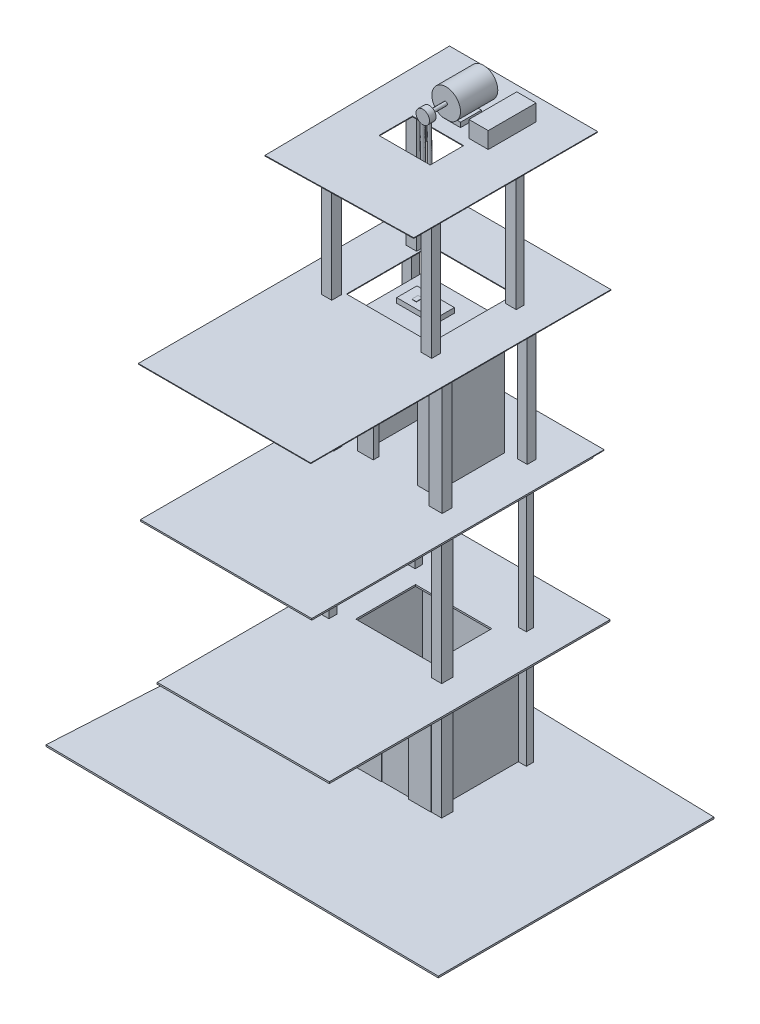
SolidWorks part; units mm, degrees
ref_plane "Front Plane" through (0, 0, 0) normal (0, 0, 1) x (1, 0, 0)
ref_plane "Top Plane" through (0, 0, 0) normal (0, 1, 0) x (1, 0, 0)
ref_plane "Right Plane" through (0, 0, 0) normal (1, 0, 0) x (0, 0, -1)
sketch "Sketch1" plane through (0, 0, 0) normal (0, 1, 0) x (1, 0, 0)
  line L1 (-1119.5185, 584.2256) -> (1199.1194, 522.7665)
  line L2 (-1119.5185, 584.2256) -> (-1218.0451, -1131.0237)
  line L3 (-1218.0451, -1131.0237) -> (1199.1194, -1157.1766)
  line L4 (1199.1194, 522.7665) -> (1199.1194, -1157.1766)
  line L5 (-1119.5185, 584.2256) -> (1199.1194, -1157.1766) construction
  line L6 (-1218.0451, -1131.0237) -> (1199.1194, 522.7665) construction
  point P0 (0, 0)
  point P5 (-1081.5805, 623.8739)
  point P6 (1586.8831, -1195.646)
  point P7 (1127.9589, 475.4185)
  point P8 (1273.4422, -1106.673)
  point P9 (-1033.4428, 518.7999)
  point P10 (1127.9589, -1075.7859)
  point P11 (1094.021, 455.5568)
  point P12 (-2669.2134, -1078.1469)
  point P13 (-2449.8772, 1011.6691)
  point P14 (-1119.5185, 584.2256)
  point P15 (-1234.8964, -941.8705)
  point P16 (-1218.0451, -1131.0237)
  point P17 (1199.1194, -1157.1766)
extrude "Boss-Extrude1" add sketch "Sketch1" along normal blind 10
sketch "Sketch2" plane through (0, 10, 0) normal (0, 1, 0) x (1, 0, 0)
  line L1 (-310.9875, 262.3228) -> (311.3377, 262.3228)
  line L2 (-310.9875, 262.3228) -> (-310.9875, -313.9536)
  line L3 (-310.9875, -313.9536) -> (311.3377, -313.9536)
  line L4 (311.3377, 262.3228) -> (311.3377, -313.9536)
  line L5 (-272.0145, 218.0111) -> (278.8911, 218.0111)
  line L6 (-272.0145, 218.0111) -> (-272.0145, -277.642)
  line L7 (-272.0145, -277.642) -> (278.8911, -277.642)
  line L8 (278.8911, 218.0111) -> (278.8911, -277.642)
extrude "Boss-Extrude2" add sketch "Sketch2" along normal blind 700
sketch "Sketch3" plane through (0, 710, 0) normal (0, 1, 0) x (1, 0, 0)
  line L1 (-498.5759, 538.5603) -> (550.6847, 538.5603)
  line L2 (-498.5759, 538.5603) -> (-498.5759, -1173.1855)
  line L3 (-498.5759, -1173.1855) -> (550.6847, -1173.441)
  line L4 (550.6847, 538.5603) -> (550.6847, -1173.441)
extrude "Boss-Extrude3" add sketch "Sketch3" along normal blind 10
sketch "Sketch4" plane through (0, 0, 313.9536) normal (0, 0, 1) x (1, 0, 0)
  line L1 (-169.9016, 641.4575) -> (173.8441, 641.4575)
  line L2 (-169.9016, 641.4575) -> (-169.9016, 10)
  line L3 (-169.9016, 10) -> (173.8441, 10)
  line L4 (173.8441, 641.4575) -> (173.8441, 10)
extrude "Cut-Extrude1" cut sketch "Sketch4" against normal blind 40
sketch "Sketch5" plane through (0, 0, 313.9536) normal (0, 0, 1) x (1, 0, 0)
  line L1 (-283.6713, 474.5331) -> (-187.5856, 474.5331)
  line L2 (-283.6713, 474.5331) -> (-283.6713, 265.4455)
  line L3 (-283.6713, 265.4455) -> (-187.5856, 265.4455)
  line L4 (-187.5856, 474.5331) -> (-187.5856, 265.4455)
extrude "Boss-Extrude4" add sketch "Sketch5" along normal blind 1
sketch "Sketch6" plane through (0, 0, 314.9536) normal (0, 0, 1) x (1, 0, 0)
  line L1 (-271.1746, 418.75) -> (-195.647, 418.75)
  line L2 (-271.1746, 418.75) -> (-271.1746, 375.0617)
  line L3 (-271.1746, 375.0617) -> (-195.647, 375.0617)
  line L4 (-195.647, 418.75) -> (-195.647, 375.0617)
extrude "Cut-Extrude2" cut sketch "Sketch6" against normal blind 1
sketch "Sketch7" plane through (0, 0, 314.9536) normal (0, 0, 1) x (1, 0, 0)
  circle A0 centre (-236.0757, 343.6172) radius 20.2971
  circle A1 centre (-236.0757, 291.5015) radius 20.232
extrude "Boss-Extrude5" add sketch "Sketch7" along normal blind 1
sketch "Sketch8" plane through (0, 0, 315.9536) normal (0, 0, 1) x (1, 0, 0)
  line L0 (-248.1005, 334.3432) -> (-224.1168, 334.3432)
  line L1 (-224.1168, 334.3432) -> (-236.1087, 356.5701)
  line L2 (-236.1087, 356.5701) -> (-248.1005, 334.3432)
  line L3 (-248.1005, 300.7341) -> (-224.1168, 300.7341)
  line L4 (-224.1168, 300.7341) -> (-236.1087, 278.0211)
  line L5 (-236.1087, 278.0211) -> (-248.1005, 300.7341)
extrude "Boss-Extrude6" add sketch "Sketch8" along normal blind 1
sketch "Sketch9" plane through (-169.9016, 0, 0) normal (1, 0, 0) x (0, 0, -1)
  line L1 (-304.9322, 641.4575) -> (-277.642, 641.4575)
  line L2 (-304.9322, 641.4575) -> (-304.9322, 10)
  line L3 (-304.9322, 10) -> (-277.642, 10)
  line L4 (-277.642, 641.4575) -> (-277.642, 10)
extrude "Boss-Extrude7" add sketch "Sketch9" along normal blind 170
sketch "Sketch10" plane through (0.0984, 0, 0) normal (1, 0, 0) x (0, 0, -1)
  line L1 (-301.4683, 640.5034) -> (-277.642, 640.5034)
  line L2 (-301.4683, 640.5034) -> (-301.4683, 10)
  line L3 (-301.4683, 10) -> (-277.642, 10)
  line L4 (-277.642, 640.5034) -> (-277.642, 10)
extrude "Boss-Extrude8" add sketch "Sketch10" along normal blind 170
sketch "Sketch11" plane through (0, 0, 313.9536) normal (0, 0, 1) x (1, 0, 0)
  line L1 (-53.7077, 693.9278) -> (48.7244, 693.9278)
  line L2 (-53.7077, 693.9278) -> (-53.7077, 651.2448)
  line L3 (-53.7077, 651.2448) -> (48.7244, 651.2448)
  line L4 (48.7244, 693.9278) -> (48.7244, 651.2448)
extrude "Boss-Extrude9" add sketch "Sketch11" along normal blind 1
sketch "Sketch12" plane through (0, 0, 314.9536) normal (0, 0, 1) x (1, 0, 0)
  line L1 (-47.5467, 689.1219) -> (41.8868, 689.1219)
  line L2 (-47.5467, 689.1219) -> (-47.5467, 655.2159)
  line L3 (-47.5467, 655.2159) -> (41.8868, 655.2159)
  line L4 (41.8868, 689.1219) -> (41.8868, 655.2159)
extrude "Cut-Extrude3" cut sketch "Sketch12" against normal blind 1
sketch "Sketch13" plane through (0, 0, 313.9536) normal (0, 0, 1) x (1, 0, 0)
  line L0 (-16.1887, 682.3335) -> (-12.3636, 682.3335)
  line L1 (-12.3636, 682.3335) -> (-16.2809, 666.1802)
  line L2 (-16.2809, 666.1802) -> (-10.8261, 666.1802)
  line L3 (-5.3714, 666.1802) -> (-5.3714, 662.7972)
  line L4 (-5.3714, 662.7972) -> (-7.9099, 662.7972)
  line L5 (-21.2894, 662.7972) -> (-16.1887, 682.3335)
  line L6 (-10.8261, 671.5233) -> (-10.8261, 666.1802)
  line L7 (-10.8261, 659.937) -> (-7.9099, 659.937)
  line L8 (-7.9099, 659.937) -> (-7.9099, 662.7972)
  line L9 (-7.9099, 671.5233) -> (-10.8261, 671.5233)
  line L10 (-10.8261, 662.7972) -> (-10.8261, 659.937)
  line L11 (-7.9099, 666.1802) -> (-5.3714, 666.1802)
  line L12 (-7.9099, 666.1802) -> (-7.9099, 671.5233)
  line L13 (-10.8261, 662.7972) -> (-21.2894, 662.7972)
extrude "Boss-Extrude10" add sketch "Sketch13" along normal blind 1
sketch "Sketch14" plane through (0, 0, 313.9536) normal (0, 0, 1) x (1, 0, 0)
  line L0 (8.2825, 678.5261) -> (25.4536, 678.5261)
  line L1 (25.4536, 678.5261) -> (16.868, 660.4022)
  line L2 (16.868, 660.4022) -> (8.2825, 678.5261)
extrude "Boss-Extrude11" add sketch "Sketch14" along normal blind 1
sketch "Sketch15" plane through (0, 0, 313.9536) normal (0, 0, 1) x (1, 0, 0)
  line L0 (-253.3924, 406.4083) -> (-253.3924, 387.5651)
  line L1 (-253.3924, 387.5651) -> (-258.9323, 387.5651)
  line L2 (-258.9323, 387.5651) -> (-258.9323, 385.0304)
  line L3 (-258.9323, 385.0304) -> (-244.3761, 385.0304)
  line L4 (-244.3761, 385.0304) -> (-244.3761, 387.5681)
  line L5 (-244.3761, 387.5681) -> (-249.8802, 387.5681)
  line L6 (-249.8802, 387.5681) -> (-249.8802, 410.5631)
  line L7 (-249.8802, 410.5631) -> (-259.6929, 410.2522)
  line L8 (-259.6929, 410.2522) -> (-259.5666, 406.4083)
  line L9 (-259.5666, 406.4083) -> (-253.3924, 406.4083)
extrude "Boss-Extrude12" add sketch "Sketch15" along normal blind 1
sketch "Sketch16" plane through (0, 0, 313.9536) normal (0, 0, 1) x (1, 0, 0)
  line L0 (-235.6485, 408.4658) -> (-235.6485, 385.5858)
  line L1 (-235.6485, 385.5858) -> (-232.1063, 385.5858)
  line L2 (-232.1063, 385.5858) -> (-232.2231, 401.9914)
  line L3 (-235.6485, 408.4658) -> (-231.8951, 408.4658)
  line L4 (-231.8951, 408.4658) -> (-231.8951, 406.5499)
  line L5 (-221.9834, 403.0568) -> (-221.9834, 385.5858)
  line L6 (-221.9834, 385.5858) -> (-218.8212, 385.5858)
  line L7 (-218.8212, 385.5858) -> (-219.0863, 397.9701)
  line L8 (-208.8863, 401.5917) -> (-208.8863, 385.5858)
  line L9 (-208.8863, 385.5858) -> (-206.271, 385.5858)
  line L10 (-206.271, 385.5858) -> (-206.5126, 401.9271)
  line L11 (-219.2828, 403.1887) -> (-219.0863, 397.9701)
  arc A4 (-221.9834, 403.0568) -> (-232.2231, 401.9914) centre (-226.8379, 399.9737) ccw
  arc A6 (-208.8863, 401.5917) -> (-219.2828, 403.1887) centre (-214.4049, 400.3049) ccw
  arc A7 (-206.5126, 401.9271) -> (-220.6047, 405.4509) centre (-214.4049, 400.3049) ccw
  arc A8 (-220.6047, 405.4509) -> (-231.8951, 406.6078) centre (-226.8379, 400.2912) ccw
  line M5 (-271.1746, 418.75) -> (-271.1746, 375.0617)
  line M6 (-271.1746, 375.0617) -> (-195.647, 375.0617)
  line M7 (-195.647, 375.0617) -> (-195.647, 418.75)
  line M8 (-195.647, 418.75) -> (-271.1746, 418.75)
  line M9 (-253.3924, 387.5651) -> (-253.3924, 406.4083)
  line M10 (-253.3924, 406.4083) -> (-259.5666, 406.4083)
  line M11 (-259.5666, 406.4083) -> (-259.6929, 410.2522)
  line M12 (-259.6929, 410.2522) -> (-249.8802, 410.5631)
  line M13 (-249.8802, 410.5631) -> (-249.8802, 387.5681)
  line M14 (-249.8802, 387.5681) -> (-244.3761, 387.5681)
  line M15 (-244.3761, 387.5681) -> (-244.3761, 385.0304)
  line M16 (-244.3761, 385.0304) -> (-258.9323, 385.0304)
  line M17 (-258.9323, 385.0304) -> (-258.9323, 387.5651)
  line M18 (-258.9323, 387.5651) -> (-253.3924, 387.5651)
extrude "Cut-Extrude4" cut sketch "Sketch16" against normal blind 2 contours A8 A7 L10 L9 L8 A6 L11 L7 L6 L5 A4 L2 L1 L0 L3 L4 M8 M5 M6 M7 M18 M9 M10 M11 M12 M13 M14 M15 M16 M17 region at (-233.4108, 417.8775, 313.9536)
sketch "Sketch17" plane through (0, 0, 311.9536) normal (0, 0, 1) x (1, 0, 0)
  line L1 (-271.2094, 458.8572) -> (-195.647, 458.8572)
  line L2 (-271.2094, 458.8572) -> (-271.2094, 418.4414)
  line L3 (-271.2094, 418.4414) -> (-195.7041, 418.4414)
  line L4 (-195.647, 458.8572) -> (-195.7041, 418.4414)
extrude "Cut-Extrude5" cut sketch "Sketch17" against normal blind 1
sketch "Sketch18" plane through (0, 0, 314.9536) normal (0, 0, 1) x (1, 0, 0)
  line L1 (-271.1417, 456.7599) -> (-195.647, 456.7599)
  line L2 (-271.1417, 456.7599) -> (-271.1417, 418.75)
  line L3 (-271.1417, 418.75) -> (-195.647, 418.75)
  line L4 (-195.647, 456.7599) -> (-195.647, 418.75)
extrude "Cut-Extrude6" cut sketch "Sketch18" against normal blind 3
sketch "Sketch19" plane through (0, 0, 310.9536) normal (0, 0, 1) x (1, 0, 0)
  line L0 (-254.3129, 446.7406) -> (-254.3129, 426.3557)
  line L1 (-254.3129, 426.3557) -> (-259.3962, 426.3557)
  line L2 (-259.3962, 426.3557) -> (-259.3962, 423.275)
  line L3 (-259.3962, 423.275) -> (-244.6783, 423.275)
  line L4 (-244.6783, 423.275) -> (-244.6783, 426.3453)
  line L5 (-244.6783, 426.3453) -> (-250.7281, 426.3453)
  line L6 (-250.7281, 426.3453) -> (-250.7281, 450.1154)
  line L7 (-250.7281, 450.1154) -> (-259.3962, 450.1154)
  line L8 (-259.3962, 450.1154) -> (-259.3962, 446.7406)
  line L9 (-259.3962, 446.7406) -> (-254.3129, 446.7406)
extrude "Boss-Extrude14" add sketch "Sketch19" along normal blind 2
sketch "Sketch20" plane through (0, 0, 310.9536) normal (0, 0, 1) x (1, 0, 0)
  line L0 (-231.7389, 449.8367) -> (-231.7389, 423.3615)
  line L1 (-231.7389, 423.3615) -> (-228.298, 423.3615)
  line L2 (-228.298, 423.3615) -> (-228.1456, 436.3278)
  line L3 (-231.7389, 449.8367) -> (-231.7389, 450.2937)
  line L4 (-231.7389, 450.2937) -> (-228.6156, 450.2937)
  line L5 (-228.6156, 450.2937) -> (-228.5661, 449.4447)
  line L6 (-228.5661, 446.4929) -> (-228.298, 439.2366)
  arc A0 (-228.1456, 436.3278) -> (-228.5661, 449.4447) centre (-224.524, 443.0091) ccw
  arc A1 (-228.298, 439.2366) -> (-228.5661, 446.4929) centre (-224.524, 443.0091) ccw
extrude "Boss-Extrude15" add sketch "Sketch20" along normal blind 2
sketch "Sketch21" plane through (0, 10, 0) normal (0, 1, 0) x (1, 0, 0)
  line L1 (-370.2495, 258.4828) -> (-312.2078, 258.4828)
  line L2 (-370.2495, 258.4828) -> (-370.2495, 212.8366)
  line L3 (-370.2495, 212.8366) -> (-312.2078, 212.8366)
  line L4 (-312.2078, 258.4828) -> (-312.2078, 212.8366)
  line L5 (-365.6413, -265.0657) -> (-310.9875, -265.0657)
  line L6 (-365.6413, -265.0657) -> (-365.6413, -313.9536)
  line L7 (-365.6413, -313.9536) -> (-310.9875, -313.9536)
  line L8 (-310.9875, -265.0657) -> (-310.9875, -313.9536)
  line L9 (311.5366, -242.3922) -> (375.3624, -242.3922)
  line L10 (311.5366, -242.3922) -> (311.5366, -312.5459)
  line L11 (311.5366, -312.5459) -> (375.3624, -312.5459)
  line L12 (375.3624, -242.3922) -> (375.3624, -312.5459)
  line L13 (311.3377, 262.3228) -> (359.7161, 262.3228)
  line L14 (311.3377, 262.3228) -> (311.3377, 218.7516)
  line L15 (311.3377, 218.7516) -> (359.7161, 218.7516)
  line L16 (359.7161, 262.3228) -> (359.7161, 218.7516)
  point P16 (345.8031, 229.2992)
extrude "Boss-Extrude16" add sketch "Sketch21" along normal blind 1600
sketch "Sketch22" plane through (0, 720, 0) normal (0, 1, 0) x (1, 0, 0)
  line L1 (-227.8036, 130.7691) -> (237.8382, 130.7691)
  line L2 (-227.8036, 130.7691) -> (-227.8036, -233.8627)
  line L3 (-227.8036, -233.8627) -> (237.8382, -233.8627)
  line L4 (237.8382, 130.7691) -> (237.8382, -233.8627)
extrude "Cut-Extrude7" cut sketch "Sketch22" against normal blind 70
sketch "Sketch23" plane through (0, 1610, 0) normal (0, 1, 0) x (1, 0, 0)
  line L1 (-509.8769, 452.1824) -> (534.1888, 452.1824)
  line L2 (-509.8769, 452.1824) -> (-509.8769, -1263.8932)
  line L3 (-509.8769, -1263.8932) -> (534.1888, -1263.8932)
  line L4 (534.1888, 452.1824) -> (534.1888, -1263.8932)
extrude "Boss-Extrude18" add sketch "Sketch23" along normal blind 5
sketch "Sketch24" plane through (0, 1615, 0) normal (0, 1, 0) x (1, 0, 0)
  line L1 (-210.3928, 199.4466) -> (247.2278, 199.4466)
  line L2 (-210.3928, 199.4466) -> (-210.3928, -239.2818)
  line L3 (-210.3928, -239.2818) -> (247.2278, -239.2818)
  line L4 (247.2278, 199.4466) -> (247.2278, -239.2818)
  line L5 (-190.4374, 157.98) -> (218.1458, 157.98)
  line L6 (-190.4374, 157.98) -> (-190.4374, -203.9085)
  line L7 (-190.4374, -203.9085) -> (218.1458, -203.9085)
  line L8 (218.1458, 157.98) -> (218.1458, -203.9085)
extrude "Boss-Extrude19" add sketch "Sketch24" along normal blind 700
sketch "Sketch25" plane through (0, 0, 239.2818) normal (0, 0, 1) x (1, 0, 0)
  line L1 (-115.2948, 2253.91) -> (153.8552, 2253.91)
  line L2 (-115.2948, 2253.91) -> (-115.2948, 1615)
  line L3 (-115.2948, 1615) -> (153.8552, 1615)
  line L4 (153.8552, 2253.91) -> (153.8552, 1615)
extrude "Cut-Extrude8" cut sketch "Sketch25" against normal blind 40
sketch "Sketch26" plane through (0, 1615, 0) normal (0, 1, 0) x (1, 0, 0)
  line L1 (-392.0328, 260.8249) -> (-332.3431, 260.8249)
  line L2 (-392.0328, 260.8249) -> (-392.0328, 211.3493)
  line L3 (-392.0328, 211.3493) -> (-332.3431, 211.3493)
  line L4 (-332.3431, 260.8249) -> (-332.3431, 211.3493)
  line L5 (-362.188, -262.1021) -> (-282.7219, -262.1021)
  line L6 (-362.188, -262.1021) -> (-362.188, -314.4144)
  line L7 (-362.188, -314.4144) -> (-282.7219, -314.4144)
  line L8 (-282.7219, -262.1021) -> (-282.7219, -314.4144)
  line L9 (317.4199, 260.5296) -> (377.7458, 260.5296)
  line L10 (317.4199, 260.5296) -> (317.4199, 206.3146)
  line L11 (317.4199, 206.3146) -> (377.7458, 206.3146)
  line L12 (377.7458, 260.5296) -> (377.7458, 206.3146)
  line L13 (296.7901, -252.3262) -> (377.7458, -252.3262)
  line L14 (296.7901, -252.3262) -> (296.7901, -312.0443)
  line L15 (296.7901, -312.0443) -> (377.7458, -312.0443)
  line L16 (377.7458, -252.3262) -> (377.7458, -312.0443)
extrude "Boss-Extrude20" add sketch "Sketch26" along normal blind 800
sketch "Sketch28" plane through (0, 2315, 0) normal (0, 1, 0) x (1, 0, 0)
  line L1 (266.1556, 199.4466) -> (-253.0902, 199.4466)
  line L2 (266.1556, 199.4466) -> (266.1556, -239.2818)
  line L3 (266.1556, -239.2818) -> (-253.0902, -239.2818)
  line L4 (-253.0902, 199.4466) -> (-253.0902, -239.2818)
extrude "Boss-Extrude21" add sketch "Sketch28" along normal blind 4
sketch "Sketch29" plane through (0, 2319, 0) normal (0, 1, 0) x (1, 0, 0)
  line L1 (57.1272, 82.8953) -> (-171.3197, 82.8953)
  line L2 (57.1272, 82.8953) -> (57.1272, -40.6557)
  line L3 (57.1272, -40.6557) -> (-171.3197, -40.6557)
  line L4 (-171.3197, 82.8953) -> (-171.3197, -40.6557)
extrude "Boss-Extrude22" add sketch "Sketch29" along normal blind 30
sketch "Sketch30" plane through (0, 1615, 0) normal (0, 1, 0) x (1, 0, 0)
  line L1 (534.1888, 518.807) -> (-509.8769, 518.807)
  line L2 (534.1888, 518.807) -> (534.1888, -1263.8932)
  line L3 (534.1888, -1263.8932) -> (-509.8769, -1263.8932)
  line L4 (-509.8769, 518.807) -> (-509.8769, -1263.8932)
extrude "Boss-Extrude23" add sketch "Sketch30" along normal blind 4
sketch "Sketch31" plane through (0, 2415, 0) normal (0, 1, 0) x (1, 0, 0)
  line L1 (509.5029, 584.8272) -> (-541.0801, 584.8272)
  line L2 (509.5029, 584.8272) -> (509.5029, -1245.8933)
  line L3 (509.5029, -1245.8933) -> (-541.0801, -1245.8933)
  line L4 (-541.0801, 584.8272) -> (-541.0801, -1245.8933)
extrude "Boss-Extrude24" add sketch "Sketch31" along normal blind 4
sketch "Sketch32" plane through (0, 2419, 0) normal (0, 1, 0) x (1, 0, 0)
  line L1 (-273.2763, 267.1919) -> (241.7138, 267.1919)
  line L2 (-273.2763, 267.1919) -> (-273.2763, -244.6131)
  line L3 (-273.2763, -244.6131) -> (241.7138, -244.6131)
  line L4 (241.7138, 267.1919) -> (241.7138, -244.6131)
extrude "Cut-Extrude9" cut sketch "Sketch32" against normal blind 4
sketch "Sketch33" plane through (0, 2419, 0) normal (0, 1, 0) x (1, 0, 0)
  line L1 (-348.3927, 194.6348) -> (-285.0254, 194.6348)
  line L2 (-348.3927, 194.6348) -> (-348.3927, 250.7404)
  line L3 (-348.3927, 250.7404) -> (-285.0254, 250.7404)
  line L4 (-285.0254, 194.6348) -> (-285.0254, 250.7404)
  line L5 (-348.3927, -322.8817) -> (-285.0254, -322.8817)
  line L6 (-348.3927, -322.8817) -> (-348.3927, -262.5669)
  line L7 (-348.3927, -262.5669) -> (-285.0254, -262.5669)
  line L8 (-285.0254, -322.8817) -> (-285.0254, -262.5669)
  line L9 (260.001, -324.9173) -> (326.8178, -324.9173)
  line L10 (260.001, -324.9173) -> (260.001, -272.0698)
  line L11 (260.001, -272.0698) -> (326.8178, -272.0698)
  line L12 (326.8178, -324.9173) -> (326.8178, -272.0698)
  line L13 (260.001, 190.1754) -> (326.8178, 190.1754)
  line L14 (260.001, 190.1754) -> (260.001, 238.0831)
  line L15 (260.001, 238.0831) -> (326.8178, 238.0831)
  line L16 (326.8178, 190.1754) -> (326.8178, 238.0831)
extrude "Boss-Extrude25" add sketch "Sketch33" along normal blind 800
sketch "Sketch34" plane through (0, 3219, 0) normal (0, 1, 0) x (1, 0, 0)
  line L1 (438.8935, 574.7386) -> (-464.6289, 574.7386)
  line L2 (438.8935, 574.7386) -> (438.8935, -546.4396)
  line L3 (438.8935, -546.4396) -> (-449.6246, -565.2649)
  line L4 (-464.6289, 574.7386) -> (-449.6246, -565.2649)
  line L5 (104.6135, 91.9277) -> (-207.4731, 91.9277)
  line L6 (104.6135, 91.9277) -> (104.6135, -112.4976)
  line L7 (104.6135, -112.4976) -> (-207.4731, -112.4976)
  line L8 (-207.4731, 91.9277) -> (-207.4731, -112.4976)
extrude "Boss-Extrude26" add sketch "Sketch34" along normal blind 4
sketch "Sketch35" plane through (0, 3223, 0) normal (0, 1, 0) x (1, 0, 0)
  line L1 (-111.9386, 304.9138) -> (0, 304.9138)
  line L2 (-111.9386, 304.9138) -> (-111.9386, 177.0343)
  line L3 (-111.9386, 177.0343) -> (0, 177.0343)
  line L4 (0, 304.9138) -> (0, 177.0343)
extrude "Boss-Extrude27" add sketch "Sketch35" along normal blind 30
sketch "Sketch36" plane through (0, 3253, 0) normal (0, 1, 0) x (1, 0, 0)
  line L1 (-197.8726, 375.6473) -> (81.8348, 375.6473)
  line L2 (-197.8726, 375.6473) -> (-197.8726, 148.2555)
  line L3 (-197.8726, 148.2555) -> (81.8348, 148.2555)
  line L4 (81.8348, 375.6473) -> (81.8348, 148.2555)
extrude "Boss-Extrude28" add sketch "Sketch36" along normal blind 200
sketch "Sketch37" plane through (0, 0, -148.2555) normal (0, 0, 1) x (1, 0, 0)
  line L0 (-36.5137, 3251.8374) -> (81.8348, 3251.4916)
  line L1 (-197.8726, 3453) -> (81.8348, 3453)
  line L2 (-197.8726, 3453) -> (-197.8726, 3252.3089)
  line L3 (-197.8726, 3252.3089) -> (-80.9439, 3251.9672)
  line L4 (81.8348, 3453) -> (81.8348, 3251.4916)
  arc A0 (-36.5137, 3251.8374) -> (-80.9439, 3251.9672) centre (-58.4819, 3336.3791) ccw
  point P5 (-80.9417, 3252.8877)
  point P6 (-58.7053, 3337.6637)
  point P9 (-36.5137, 3251.9672)
extrude "Cut-Extrude12" cut sketch "Sketch37" against normal blind 300
sketch "Sketch38" plane through (0, 3223, 0) normal (0, 1, 0) x (1, 0, 0)
  line L1 (82.3765, 437.8048) -> (200.0694, 437.8048)
  line L2 (82.3765, 437.8048) -> (82.3765, 146.1268)
  line L3 (82.3765, 146.1268) -> (200.0694, 146.1268)
  line L4 (200.0694, 437.8048) -> (200.0694, 146.1268)
extrude "Boss-Extrude30" add sketch "Sketch38" along normal blind 100
sketch "Sketch39" plane through (0, 0, -148.2555) normal (0, 0, 1) x (1, 0, 0)
  circle A0 centre (-61.6258, 3334.5719) radius 10.8281
extrude "Boss-Extrude31" add sketch "Sketch39" along normal blind 100
sketch "Sketch40" plane through (0, 0, -48.2555) normal (0, 0, 1) x (1, 0, 0)
  circle A0 centre (-61.2375, 3333.5153) radius 41.0186
  point P2 (-61.2375, 3333.5153)
extrude "Boss-Extrude32" add sketch "Sketch40" along normal blind 40
sketch "Sketch41" plane through (0, 2349, 0) normal (0, 1, 0) x (1, 0, 0)
  line L1 (-115.5151, 33.8271) -> (-88.069, 33.8271)
  line L2 (-115.5151, 33.8271) -> (-115.5151, -3.9297)
  line L3 (-115.5151, -3.9297) -> (-88.069, -3.9297)
  line L4 (-88.069, 33.8271) -> (-88.069, -3.9297)
  line L5 (-3.1738, 33.8271) -> (21.6081, 33.8271)
  line L6 (-3.1738, 33.8271) -> (-3.1738, -3.9297)
  line L7 (-3.1738, -3.9297) -> (21.6081, -3.9297)
  line L8 (21.6081, 33.8271) -> (21.6081, -3.9297)
extrude "Boss-Extrude33" add sketch "Sketch41" along normal blind 2
sketch "Sketch44" plane through (0, 2349, 0) normal (0, 1, 0) x (1, 0, 0)
  circle A0 centre (-69.8187, 25.1407) radius 11.4671
sketch3d "3DSketch3"
  line L0 (-69.8187, 2349, -25.1407) -> (-79.1852, 3344.6746, -25.1407)
sweep "Sweep2" add profiles "Sketch44" path "3DSketch3"
sketch "Sketch46" plane through (0, 2349, 0) normal (0, 1, 0) x (1, 0, 0)
  circle A0 centre (-25.0699, 26.1332) radius 9.8236
sketch3d "3DSketch5"
  line L0 (-25.0699, 2349, -26.1332) -> (-39.6492, 3323.4674, -26.1332)
sweep "Sweep3" add profiles "Sketch46" path "3DSketch5"
sketch "Sketch47" plane through (0, 0, 0) normal (0, -1, 0) x (-1, 0, 0)
  line L1 (307.844, -399.3506) -> (-315.4623, -399.3506)
  line L2 (307.844, -399.3506) -> (307.844, 171.3279)
  line L3 (307.844, 171.3279) -> (-315.4623, 171.3279)
  line L4 (-315.4623, -399.3506) -> (-315.4623, 171.3279)
  line L5 (284.1002, -349.204) -> (-265.7287, -349.204)
  line L6 (284.1002, -349.204) -> (284.1002, 113.2378)
  line L7 (284.1002, 113.2378) -> (-265.7287, 113.2378)
  line L8 (-265.7287, -349.204) -> (-265.7287, 113.2378)
extrude "Boss-Extrude34" add sketch "Sketch47" along normal blind 300
sketch "Sketch48" plane through (0, 0, 399.3506) normal (0, 0, 1) x (1, 0, 0)
  line L1 (-252.9384, -33.6607) -> (262.0186, -33.6607)
  line L2 (-252.9384, -33.6607) -> (-252.9384, -300)
  line L3 (-252.9384, -300) -> (262.0186, -300)
  line L4 (262.0186, -33.6607) -> (262.0186, -300)
extrude "Cut-Extrude13" cut sketch "Sketch48" against normal blind 60
sketch "Sketch49" plane through (0, -300, 0) normal (0, -1, 0) x (-1, 0, 0)
  line L1 (307.3968, -399.3647) -> (-315.4623, -399.3647)
  line L2 (307.3968, -399.3647) -> (307.3968, 171.3279)
  line L3 (307.3968, 171.3279) -> (-315.4623, 171.3279)
  line L4 (-315.4623, -399.3647) -> (-315.4623, 171.3279)
extrude "Boss-Extrude35" add sketch "Sketch49" along normal blind 30
